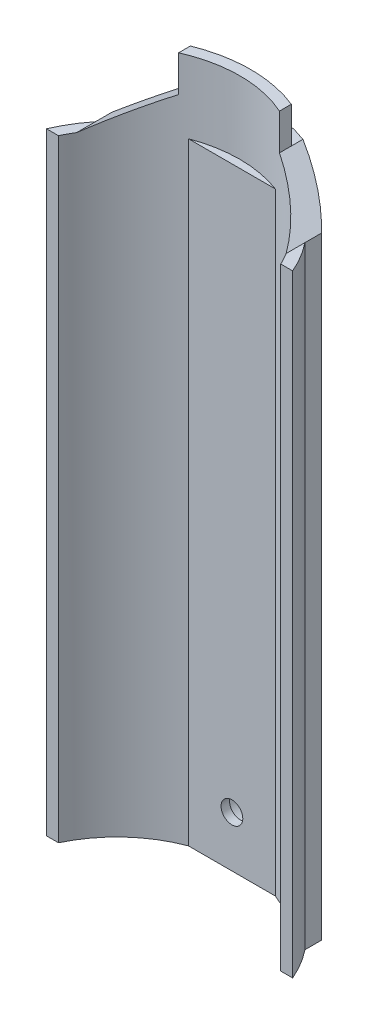
SolidWorks part; units mm, degrees
ref_plane "前视基准面" through (0, 0, 0) normal (0, 0, 1) x (1, 0, 0)
ref_plane "上视基准面" through (0, 0, 0) normal (0, 1, 0) x (1, 0, 0)
ref_plane "右视基准面" through (0, 0, 0) normal (1, 0, 0) x (0, 0, -1)
other "Configuration Table"
sketch "草图1" plane through (0, 0, 0) normal (0, 1, 0) x (1, 0, 0)
  circle A0 centre (0, 0) radius 20
  circle A1 centre (0, 0) radius 17
  dimension "D1" = 40
  dimension "D2" = 34
extrude "凸台-拉伸1" add sketch "草图1" along normal blind 80.6
sketch "草图2" plane through (0, 0, 0) normal (0, 0, 1) x (1, 0, 0)
  line L0 (-14.47, 0) -> (14.47, 0) construction
  line L1 (-20, 0) -> (20, 0) construction
  line L3 (-14.47, 0) -> (-20, 0)
  line L4 (-14.47, 0) -> (-14.47, 80.6)
  line L5 (-14.47, 80.6) -> (-20, 80.6)
  line L6 (-20, 0) -> (-20, 80.6)
  line L7 (14.47, 0) -> (20, 0)
  line L8 (14.47, 0) -> (14.47, 80.6)
  line L9 (14.47, 80.6) -> (20, 80.6)
  line L10 (20, 0) -> (20, 80.6)
  point P6 (0, 0)
  dimension "D1" = 28.94
extrude "切除-拉伸1" cut sketch "草图2" against normal through all
sketch "草图3" plane through (0, 0, 0) normal (0, 0, 1) x (1, 0, 0)
  line L0 (-6.97, 80.6) -> (6.97, 80.6) construction
  line L1 (14.47, 80.6) -> (-14.47, 80.6) construction
  line L3 (-6.97, 80.6) -> (-14.47, 75.6)
  line L8 (-14.47, 0) -> (-14.47, 80.6) construction
  line L10 (6.97, 80.6) -> (14.47, 75.6)
  line L11 (14.47, 80.6) -> (14.47, 0) construction
  line L12 (14.47, 75.6) -> (14.47, 80.6)
  line L13 (14.47, 80.6) -> (6.97, 80.6)
  line L14 (-14.47, 75.6) -> (-14.47, 80.6)
  line L15 (-14.47, 80.6) -> (-6.97, 80.6)
  point P5 (0, 80.6)
  dimension "D1" = 13.94
  dimension "D2" = 5
  dimension "D3" = 7.5
  dimension "D4" = 5
extrude "切除-拉伸2" cut sketch "草图3" against normal through all
sketch "草图4" plane through (0, 0, 0) normal (0, 1, 0) x (1, 0, 0)
  line L0 (0, -1000) -> (0, 49000) construction
  line L1 (-17, 7.2973) -> (-15.3542, 7.2973)
  line L2 (15.3542, 7.2973) -> (17, 7.2973)
  arc A0 (15.3542, 7.2973) -> (-15.3542, 7.2973) centre (0, 0) ccw
  arc A1 (17, 7.2973) -> (-17, 7.2973) centre (0, 0) ccw
  point P9 (0, 7.2973)
  dimension "D1" = 34
  dimension "D2" = 37
  dimension "D3" = 34
extrude "凸台-拉伸3" add sketch "草图4" along normal blind 75.6
sketch "草图5" plane through (0, 0, 0) normal (0, 1, 0) x (1, 0, 0)
  line L0 (0, -1000) -> (0, 49000) construction
  line L1 (-6.97, 17.1368) -> (6.97, 17.1368) construction
  line L2 (6.97, 17.1368) -> (6.97, 15.5055)
  line L3 (-6.97, 17.1368) -> (-6.97, 15.5055)
  arc A0 (6.97, 17.1368) -> (-6.97, 17.1368) centre (0, 0) ccw
  arc A2 (6.97, 15.5055) -> (-6.97, 15.5055) centre (0, 0) ccw
  point P11 (0, 17.1368)
  dimension "D1" = 13.94
extrude "凸台-拉伸5" add sketch "草图5" along normal blind 5 from surface starting at face at (0, 80.6, -17.8129)
sketch "草图6" plane through (0, 0, 0) normal (0, 1, 0) x (1, 0, 0)
  line L4 (14.47, 11.5269) -> (14.47, 13.8065)
  line L5 (15.3542, 7.2973) -> (17, 7.2973)
  line L6 (-17, 7.2973) -> (-15.3542, 7.2973)
  line L7 (-14.47, 13.8065) -> (-14.47, 11.5269)
  line L8 (14.47, 11.5269) -> (14.47, 13.8065)
  line L9 (15.3542, 7.2973) -> (17, 7.2973)
  line L10 (-17, 7.2973) -> (-15.3542, 7.2973)
  line L11 (-14.47, 13.8065) -> (-14.47, 11.5269)
  arc A4 (17, 7.2973) -> (14.47, 11.5269) centre (0, 0) ccw
  arc A5 (15.3542, 7.2973) -> (-15.3542, 7.2973) centre (0, 0) ccw
  arc A6 (-14.47, 11.5269) -> (-17, 7.2973) centre (0, 0) ccw
  arc A7 (14.47, 13.8065) -> (-14.47, 13.8065) centre (0, 0) ccw
  arc A8 (17, 7.2973) -> (14.47, 11.5269) centre (0, 0) ccw
  arc A9 (15.3542, 7.2973) -> (-15.3542, 7.2973) centre (0, 0) ccw
  arc A10 (-14.47, 11.5269) -> (-17, 7.2973) centre (0, 0) ccw
  arc A11 (14.47, 13.8065) -> (-14.47, 13.8065) centre (0, 0) ccw
  dimension "D1" = 0
extrude "凸台-拉伸6" add sketch "草图6" against normal blind 9
sketch "草图7" plane through (0, 0, 0) normal (0, 1, 0) x (1, 0, 0)
  line L0 (0, -1000) -> (0, 49000) construction
  line L1 (-6, 15.906) -> (6, 15.906)
  arc A0 (6, 15.906) -> (-6, 15.906) centre (0, 0) ccw
  point P6 (0, 0)
  point P9 (0, 15.906)
  dimension "D1" = 12
extrude "凸台-拉伸7" add sketch "草图7" along normal up to vertex (75.6 mm away) from surface up to point (-14.47, 75.6, -8.923) starting at face at (0, -9, -11.9902)
sketch "草图8" plane through (0, 0, 0) normal (0, 1, 0) x (1, 0, 0)
  line L0 (6, 15.906) -> (6, 19.0788) construction
  line L1 (6, 19.0788) -> (-6, 19.0788)
  line L2 (-6, 19.0788) -> (-6, 15.906) construction
  arc A0 (14.47, 13.8065) -> (-14.47, 13.8065) centre (0, 0) ccw construction
  arc A1 (6, 19.0788) -> (-6, 19.0788) centre (0, 0) ccw
extrude "切除-拉伸3" cut sketch "草图8" along normal blind 15 from surface starting at face at (0, -9, -11.9845)
sketch "草图9" plane through (0, 0, 0) normal (0, 0, 1) x (1, 0, 0)
  circle A0 centre (0, -1.9845) radius 1.5
  dimension "D1" = 3
extrude "切除-拉伸4" cut sketch "草图9" against normal through all
sketch "草图10" plane through (0, 0, 0) normal (0, 0, 1) x (1, 0, 0)
  circle A0 centre (0, -1.9845) radius 2.6
  dimension "D1" = 5.2
extrude "切除-拉伸5" cut sketch "草图10" along normal blind 2 from surface starting at face at (-1.5, -1.9845, -19.0788)
sketch "草图11" plane through (0, 0, 0) normal (0, 0, 1) x (1, 0, 0)
  line L0 (6, 6) -> (2, 6)
  line L1 (-6, 6) -> (6, 6) construction
  line L2 (2, 6) -> (6, 1.25)
  line L3 (6, 6) -> (6, -9) construction
  line L4 (6, 1.25) -> (6, 6)
  line L5 (-6, 6) -> (-2, 6)
  line L6 (-6, 6) -> (6, 6) construction
  line L7 (-2, 6) -> (-6, 1.25)
  line L8 (-6, 6) -> (-6, -9) construction
  line L9 (-6, 1.25) -> (-6, 6)
  dimension "D1" = 4.75
  dimension "D2" = 4
  dimension "D3" = 4
  dimension "D4" = 4.75
extrude "凸台-拉伸8" add sketch "草图11" against normal up to surface (0.821 mm away) from surface up to face at (0, 28.8026, -17.3135) starting at face at (-2.6, -1.9845, -19.0788)
